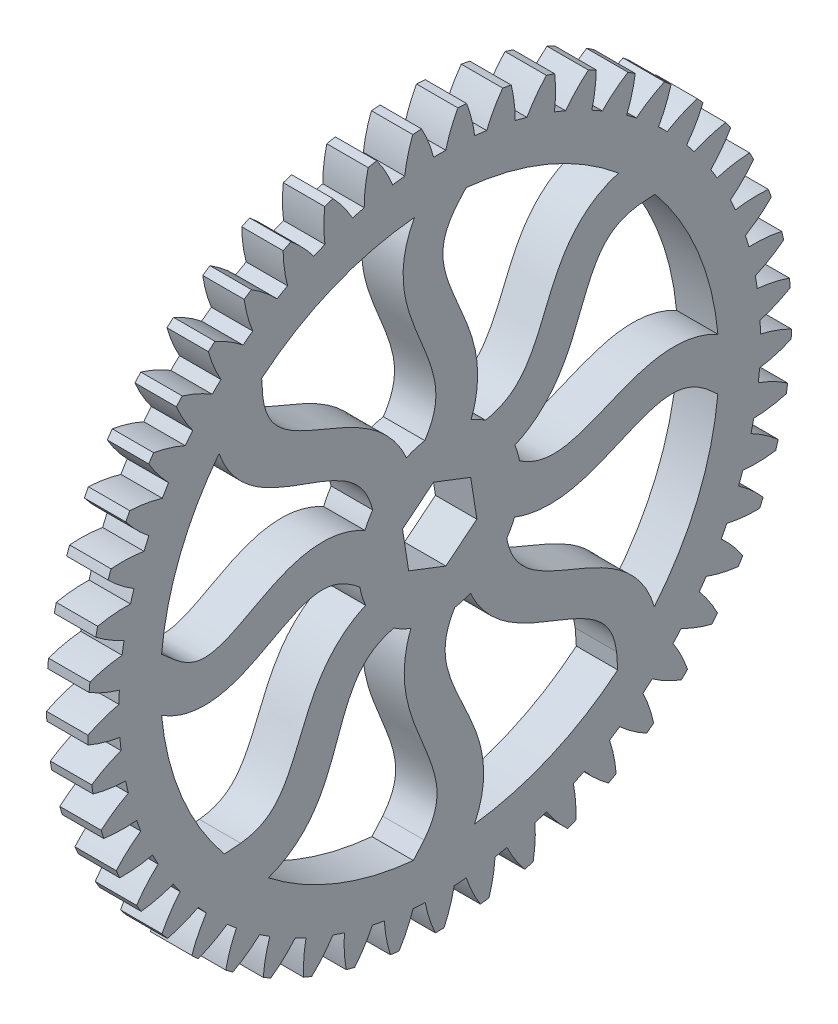
SolidWorks part; units mm, degrees
material "Plain Carbon Steel"
ref_plane "Plane1" through (0, 0, 0) normal (0, 0, 1) x (1, 0, 0)
ref_plane "Plane2" through (0, 0, 0) normal (0, 1, 0) x (1, 0, 0)
ref_plane "Plane3" through (0, 0, 0) normal (1, 0, 0) x (0, 0, -1)
sketch "HoldingSke" plane through (0, 0, 0) normal (0, 1, 0) x (1, 0, 0)
  line L0 (0, 0) -> (0.6561, -0.7547)
  line L1 (-15, 0) -> (100, 0) construction
  line L2 (0, 0) -> (-2.1039, 2.3779)
  line L3 (0, 0) -> (-11.863, 4.5341)
  line L4 (0, 0) -> (5.6657, 6.5177)
  line L5 (0, 0) -> (-46.8476, -17.4728)
  line L6 (0, 0) -> (-2.4869, -1.6779)
  line L7 (-2.1039, 2.3779) -> (8.6586, 51.2059)
  line L8 (-76.2, 54.61) -> (-75.7, 54.61)
  line L9 (-71.009, 38.7566) -> (-53.1078, 45.2721)
  line L10 (-76.2, 71.12) -> (104.1128, 71.12)
  line L11 (0, 0) -> (-3, 0)
  line L12 (-76.2, 101.6) -> (-76.162, 101.6)
  line L13 (24.9733, 27.94) -> (52.9518, 28.4284)
  line L14 (24.9733, 27.94) -> (24.9743, 27.94)
  line L15 (24.9733, 27.94) -> (100.4006, 29.5858)
  line L16 (-63.627, -1) -> (-12.827, -1)
  circle A0 centre (0, 0) radius 1.5
  circle A1 centre (0, 0) radius 23.249
  circle A2 centre (0, 0) radius 37.5
  circle A3 centre (0, 0) radius 1.5
  dimension "MHD" = 46.498
  dimension "Hub_dia" = 75
  dimension "Bore" = 3
  dimension "MBD" = 3
  dimension "Num_teeth" = 49
  dimension "Pitch_radius" = 180.3128
  dimension "Pitch" = 1
  dimension "Width" = 3
  dimension "Overall_len" = 50
  dimension "Show_teeth" = 49
  dimension "Thickness" = 3
  dimension "OAL" = 50.0001
  dimension "T_dim" = 0.5
  dimension "Ap" = 20
  dimension "H" = 19.05
  dimension "Backlash" = 0.038
  dimension "Addendum_fac" = 1
  dimension "Dedendum_fac" = 1.25
  dimension "Clearance_fac" = 0.25
  dimension "Dedendum_add" = 0.001
  dimension "Module" = 1
sketch "BasProSke" plane through (0, 0, 0) normal (0, 1, 0) x (1, 0, 0)
  line L0 (-10, 0) -> (60, 0) construction
  line L1 (0, 0) -> (0, 25.5)
  line L2 (0, 0) -> (3, 0)
  line L3 (3, 0) -> (3, 25.5)
  line L4 (3, 25.5) -> (0, 25.5)
  dimension "Diameter" = 51
  dimension "Thickness" = 3
revolve "Base-Revolve" add sketch "BasProSke" angle 360 about L0
sketch "TooCutSke" plane through (0, 0, 0) normal (1, 0, 0) x (0, 0, -1)
  line L1 (0, 0) -> (0, 107) construction
  line L2 (0, 0) -> (-0.8518, 24.4852) construction
  line L3 (0, 0) -> (-3.1381, 48.8783) construction
  line L4 (-0.8518, 24.4852) -> (-1.569, 24.4391) construction
  arc A0 (0.4386, 23.2449) -> (-0.4386, 23.2449) centre (0, 0) ccw
  arc A1 (1.3315, 25.4906) -> (-1.3315, 25.4906) centre (0, 0) ccw
  circle A2 centre (0, 0) radius 24.5 construction
  circle A3 centre (0, 0) radius 23.0225 construction
  arc A4 (-0.4386, 23.2449) -> (-1.3315, 25.4906) centre (-9.9221, 20.7746) ccw
  arc A5 (1.3315, 25.4906) -> (0.4386, 23.2449) centre (9.9221, 20.7746) ccw
  dimension "Root_dia" = 46.498
  dimension "Overcut_dia" = 51.0508
  dimension "Pitch_dia" = 49
  dimension "Base_dia" = 46.0449
  dimension "Flank_rad" = 9.8
  dimension "Half_ang" = 3.673
  dimension "Half_CT" = 0.7188
extrude "ToothCut" cut sketch "TooCutSke" along normal through all
fillet "Breaks" [suppressed] radius 0.02 tangent propagation no
fillet "RootFillets" [suppressed] radius 0.251
pattern_circular "TeethCuts" count 49 every 7.347 about axis through (-10, 0, 0) along (1, 0, 0) of "ToothCut", "RootFillets", "Breaks"
sketch "HubNeaOneSke" plane through (0, 0, 0) normal (-1, 0, 0) x (0, 0, 1)
  circle A0 centre (0, 0) radius 23.249
  dimension "Diameter" = 46.498
extrude "HubNearOne" [suppressed] add sketch "HubNeaOneSke" along normal blind 47.0001
sketch "HubNeaBotSke" plane through (0, 0, 0) normal (-1, 0, 0) x (0, 0, 1)
  circle A0 centre (0, 0) radius 23.249
  dimension "Diameter" = 46.498
extrude "HubNearBoth" [suppressed] add sketch "HubNeaBotSke" along normal blind 23.5
ref_plane "FarPln" through (3, 0, 0) normal (1, 0, 0) x (0, 0, -1)
sketch "HubFarSke" plane through (3, 0, 0) normal (1, 0, 0) x (0, 0, -1)
  circle A0 centre (0, 0) radius 23.249
  dimension "Diameter" = 46.498
extrude "HubFar" [suppressed] add sketch "HubFarSke" along normal blind 23.5
sketch "BorSke" plane through (0, 0, 0) normal (1, 0, 0) x (0, 0, -1)
  line L1 (-2.8868, 0) -> (-1.4434, -2.5) construction
  line L2 (-1.4434, -2.5) -> (1.4434, -2.5) construction
  line L3 (1.4434, -2.5) -> (2.8868, 0) construction
  line L4 (2.8868, 0) -> (1.4434, 2.5) construction
  line L5 (1.4434, 2.5) -> (-1.4434, 2.5) construction
  line L6 (-1.4434, 2.5) -> (-2.8868, 0) construction
  circle A0 centre (0, 0) radius 1.5
  circle A1 centre (0, 0) radius 2.5 construction
  dimension "D1" = 5
  dimension "Diameter" = 3
extrude "Bore" cut sketch "BorSke" along normal mid plane 100.0001
sketch "KeySke" plane through (0, 0, 0) normal (1, 0, 0) x (0, 0, -1)
  line L0 (-0.6, 0) -> (-0.6, 2)
  line L1 (-0.6, 2) -> (0.6, 2)
  line L2 (0.6, 2) -> (0.6, 0)
  line L3 (0, 0) -> (0, 34) construction
  line L4 (-0.6, 0) -> (0.6, 0)
  dimension "Offset" = 2
  dimension "Width" = 1.2
extrude "Keyway" [suppressed] cut sketch "KeySke" along normal mid plane 100.0001
pattern_circular "Keyway2" [suppressed] count 2 every 90 about axis through (-10, 0, 0) along (1, 0, 0)
sketch "Sketch1" plane through (0, 0, 0) normal (-1, 0, 0) x (0, 0, 1)
  line L0 (2.8868, 0) -> (5.8868, 0) construction
  line L1 (20.249, 0) -> (5.8868, 0) construction
  line L2 (20.249, 0) -> (23.249, 0) construction
  line L3 (19.2628, 1.1302) -> (20.1585, 1.9118)
  line L4 (5.7215, -1.1285) -> (4.8183, -3.3819)
  line L5 (14.42, -12.8217) -> (15.6061, -12.9024)
  line L6 (3.2477, -4.8436) -> (1.0157, -5.7985)
  line L7 (1.1302, -19.2628) -> (1.9118, -20.1585)
  line L8 (-1.1285, -5.7215) -> (-3.3819, -4.8183)
  line L9 (-12.8217, -14.42) -> (-12.9024, -15.6061)
  line L10 (-4.8436, -3.2477) -> (-5.7985, -1.0157)
  line L11 (-19.2628, -1.1302) -> (-20.1585, -1.9118)
  line L12 (-5.7215, 1.1285) -> (-4.8183, 3.3819)
  line L13 (-14.42, 12.8217) -> (-15.6061, 12.9024)
  line L14 (-3.2477, 4.8436) -> (-1.0157, 5.7985)
  line L15 (-1.1302, 19.2628) -> (-1.9118, 20.1585)
  line L16 (1.1285, 5.7215) -> (3.3819, 4.8183)
  line L17 (11.1265, 15.7649) -> (11.0739, 16.9526) [skipped]
  line L18 (4.4496, 3.7696) -> (5.6483, 1.6585) [skipped]
  line L19 (2.685, -5.1768) -> (0.3601, -5.8757) [skipped]
  line L20 (-5.3883, 18.5283) -> (-6.3496, 19.2277) [skipped]
  line L21 (12.8938, -14.3556) -> (14.0634, -14.5686) [skipped]
  line L22 (-2.3733, -5.3269) -> (-4.3693, -3.945) [skipped]
  line L23 (-5.6445, -1.4657) -> (-5.8085, 0.9564) [skipped]
  line L24 (-4.6652, 3.4992) -> (-2.8738, 5.1376) [skipped]
  line L25 (-0.173, 5.8291) -> (2.2249, 5.4501) [skipped]
  line L26 (-17.8456, 7.3395) -> (-18.9917, 7.024) [skipped]
  line L27 (-16.8648, -9.3761) -> (-17.3327, -10.469) [skipped]
  line L28 (-3.1845, -19.0313) -> (-2.6218, -20.0786) [skipped]
  line L29 (12.8217, 14.42) -> (12.9024, 15.6061)
  line L30 (4.8436, 3.2477) -> (5.7985, 1.0157)
  circle A0 centre (0, 0) radius 5.8868
  circle A1 centre (0, 0) radius 23.249 construction
  circle A2 centre (0, 0) radius 20.249
  spline S0 degree 3 poles (20.249, 0) (14.621, -4.9109) (10.9351, 5.4308) (4.7333, 0) knots 0 0 0 0 1 1 1 1 construction
  spline S1 degree 1 poles (19.2628, 1.1302) (3.7451, 1.1285) knots 0 0 1 1 construction
  spline S2 degree 3 poles (19.2628, 1.1302) (19.1293, 1.0138) (18.8376, 0.7808) (18.3339, 0.4567) (17.7715, 0.2166) (17.178, 0.1175) (16.3645, 0.1613) (15.163, 0.5668) (13.4561, 1.4991) (11.5183, 2.5306) (9.5885, 3.1305) (7.8275, 3.1388) (6.4544, 2.8313) (5.3119, 2.2876) (4.4177, 1.687) (3.9611, 1.3177) (3.7451, 1.1285) knots 0 0 0 0 0.03125 0.0625 0.125 0.1875 0.25 0.375 0.5 0.625 0.75 0.8125 0.875 0.9375 0.96875 1 1 1 1 only from (19.2628, 1.1302) to (5.4145, 2.3102)
  spline S3 degree 1 poles (21.2352, -1.1302) (5.7215, -1.1285) knots 0 0 1 1 construction
  spline S4 degree 3 poles (21.2352, -1.1302) (21.0332, -1.3065) (20.6054, -1.6485) (19.7572, -2.1994) (18.2169, -2.8765) (16.0114, -2.9359) (13.8328, -2.1307) (11.9654, -1.1014) (10.276, -0.2178) (9.0516, 0.1315) (8.1569, 0.1303) (7.4619, -0.0214) (6.7968, -0.3317) (6.2097, -0.7234) (5.8756, -0.9935) (5.7215, -1.1285) knots 0 0 0 0 0.03125 0.0625 0.125 0.25 0.375 0.5 0.625 0.75 0.8125 0.875 0.9375 0.96875 1 1 1 1 only from (20.1564, -1.9342) to (5.7215, -1.1285)
  spline S5 degree 3 poles (14.42, -12.8217) (14.2582, -12.8026) (13.9229, -12.7485) (13.3679, -12.6041) (12.7932, -12.3588) (12.2429, -11.9773) (11.6038, -11.331) (10.9146, -10.2125) (10.1792, -8.4567) (9.3709, -6.4927) (8.2199, -4.4964) (6.6749, -3.0349) (5.2192, -2.3229) (4.4625, -2.0781) (4.0808, -1.9789) (3.8352, -1.9214) (3.651, -1.8843) (3.5434, -1.8646) knots 0 0 0 0 0.03125 0.0625 0.125 0.1875 0.25 0.375 0.5 0.625 0.75 0.875 0.9375 0.96875 0.97755 0.98653 1 1 1 1
  spline S6 degree 3 poles (13.7854, -16.3368) (13.5386, -16.2959) (13.1873, -16.2223) (12.7413, -16.0987) (12.4785, -16.0136) (11.9085, -15.8059) (10.665, -15.1995) (9.1813, -13.763) (8.1187, -11.7584) (7.4026, -9.7726) (6.7462, -7.9552) (6.0949, -6.7348) (5.4563, -5.9802) (4.8946, -5.5111) (4.3092, -5.1875) (3.7476, -4.9747) (3.4115, -4.8817) (3.2477, -4.8436) knots 0 0 0 0 0.03125 0.044052 0.059677 0.06749 0.125 0.25 0.375 0.5 0.625 0.75 0.8125 0.875 0.9375 0.96875 1 1 1 1
  spline S7 degree 3 poles (1.1302, -19.2628) (1.0293, -19.1349) (0.8304, -18.8595) (0.5401, -18.365) (0.3072, -17.7851) (0.1878, -17.1263) (0.1929, -16.2173) (0.4965, -14.9391) (1.2179, -13.1776) (2.0352, -11.2173) (2.6329, -8.9918) (2.5738, -6.8659) (2.048, -5.3331) (1.686, -4.6249) (1.4863, -4.2849) (1.3532, -4.0706) (1.2492, -3.9141) (1.1871, -3.824) knots 0 0 0 0 0.03125 0.0625 0.125 0.1875 0.25 0.375 0.5 0.625 0.75 0.875 0.9375 0.96875 0.97755 0.98653 1 1 1 1
  spline S8 degree 3 poles (-1.8041, -21.2996) (-1.9497, -21.0961) (-2.1461, -20.7958) (-2.374, -20.3929) (-2.4997, -20.147) (-2.7559, -19.597) (-3.2064, -18.289) (-3.2397, -16.224) (-2.5736, -14.0552) (-1.6758, -12.1447) (-0.8549, -10.3954) (-0.4525, -9.0719) (-0.3705, -8.0869) (-0.4359, -7.3579) (-0.6211, -6.7152) (-0.8677, -6.1676) (-1.0396, -5.8641) (-1.1285, -5.7215) knots 0 0 0 0 0.03125 0.044052 0.059677 0.06749 0.125 0.25 0.375 0.5 0.625 0.75 0.8125 0.875 0.9375 0.96875 1 1 1 1
  spline S9 degree 3 poles (-12.8217, -14.42) (-12.8, -14.2585) (-12.7405, -13.9241) (-12.5872, -13.3716) (-12.3325, -12.8009) (-11.9422, -12.2568) (-11.2856, -11.6282) (-10.1561, -10.9572) (-8.3887, -10.2503) (-6.4119, -9.4739) (-4.3973, -8.3554) (-2.911, -6.8341) (-2.1755, -5.3901) (-1.9185, -4.6375) (-1.8132, -4.2575) (-1.7517, -4.0128) (-1.7116, -3.8293) (-1.6902, -3.722) knots 0 0 0 0 0.03125 0.0625 0.125 0.1875 0.25 0.375 0.5 0.625 0.75 0.875 0.9375 0.96875 0.97755 0.98653 1 1 1 1
  spline S10 degree 3 poles (-15.8291, -14.3136) (-15.7999, -14.0651) (-15.7429, -13.7108) (-15.6403, -13.2595) (-15.5677, -12.993) (-15.387, -12.4139) (-14.8397, -11.1432) (-13.4744, -9.5937) (-11.5219, -8.4381) (-9.572, -7.6296) (-7.7874, -6.8885) (-6.599, -6.1806) (-5.8752, -5.5073) (-5.433, -4.9241) (-5.1373, -4.3242) (-4.9511, -3.7532) (-4.8739, -3.4131) (-4.8436, -3.2477) knots 0 0 0 0 0.03125 0.044052 0.059677 0.06749 0.125 0.25 0.375 0.5 0.625 0.75 0.8125 0.875 0.9375 0.96875 1 1 1 1
  spline S11 degree 3 poles (-19.2628, -1.1302) (-19.1332, -1.0314) (-18.8548, -0.8369) (-18.3556, -0.5547) (-17.772, -0.3312) (-17.1113, -0.2225) (-16.2025, -0.2423) (-14.9294, -0.5664) (-13.1798, -1.3163) (-11.233, -2.1652) (-9.0175, -2.7988) (-6.8908, -2.7741) (-5.3497, -2.2731) (-4.6358, -1.9227) (-4.2926, -1.7284) (-4.0761, -1.5988) (-3.918, -1.4974) (-3.827, -1.4367) knots 0 0 0 0 0.03125 0.0625 0.125 0.1875 0.25 0.375 0.5 0.625 0.75 0.875 0.9375 0.96875 0.97755 0.98653 1 1 1 1
  spline S12 degree 3 poles (-21.3142, 1.0716) (-21.1177, 1.2266) (-20.8269, 1.4369) (-20.4352, 1.6835) (-20.1955, 1.8206) (-19.6582, 2.1023) (-18.3727, 2.6138) (-16.3116, 2.7441) (-14.1139, 2.1806) (-12.1634, 1.3735) (-10.3774, 0.6356) (-9.0365, 0.2959) (-8.0487, 0.2602) (-7.3236, 0.3598) (-6.6903, 0.575) (-6.1549, 0.847) (-5.8598, 1.033) (-5.7215, 1.1285) knots 0 0 0 0 0.03125 0.044052 0.059677 0.06749 0.125 0.25 0.375 0.5 0.625 0.75 0.8125 0.875 0.9375 0.96875 1 1 1 1
  spline S13 degree 3 poles (-14.42, 12.8217) (-14.2585, 12.8) (-13.9241, 12.7405) (-13.3716, 12.5872) (-12.8009, 12.3325) (-12.2568, 11.9422) (-11.6282, 11.2856) (-10.9572, 10.1561) (-10.2503, 8.3887) (-9.4739, 6.4119) (-8.3554, 4.3973) (-6.8341, 2.911) (-5.3901, 2.1755) (-4.6375, 1.9185) (-4.2575, 1.8132) (-4.0128, 1.7517) (-3.8293, 1.7116) (-3.722, 1.6902) knots 0 0 0 0 0.03125 0.0625 0.125 0.1875 0.25 0.375 0.5 0.625 0.75 0.875 0.9375 0.96875 0.97755 0.98653 1 1 1 1
  spline S14 degree 3 poles (-14.3136, 15.8291) (-14.0651, 15.7999) (-13.7108, 15.7429) (-13.2595, 15.6403) (-12.993, 15.5677) (-12.4139, 15.387) (-11.1432, 14.8397) (-9.5937, 13.4744) (-8.4381, 11.5219) (-7.6296, 9.572) (-6.8885, 7.7874) (-6.1806, 6.599) (-5.5073, 5.8752) (-4.9241, 5.433) (-4.3242, 5.1373) (-3.7532, 4.9511) (-3.4131, 4.8739) (-3.2477, 4.8436) knots 0 0 0 0 0.03125 0.044052 0.059677 0.06749 0.125 0.25 0.375 0.5 0.625 0.75 0.8125 0.875 0.9375 0.96875 1 1 1 1
  spline S15 degree 3 poles (-1.1302, 19.2628) (-1.0314, 19.1332) (-0.8369, 18.8548) (-0.5547, 18.3556) (-0.3312, 17.772) (-0.2225, 17.1113) (-0.2423, 16.2025) (-0.5664, 14.9294) (-1.3163, 13.1798) (-2.1652, 11.233) (-2.7988, 9.0175) (-2.7741, 6.8908) (-2.2731, 5.3497) (-1.9227, 4.6358) (-1.7284, 4.2926) (-1.5988, 4.0761) (-1.4974, 3.918) (-1.4367, 3.827) knots 0 0 0 0 0.03125 0.0625 0.125 0.1875 0.25 0.375 0.5 0.625 0.75 0.875 0.9375 0.96875 0.97755 0.98653 1 1 1 1
  spline S16 degree 3 poles (1.0716, 21.3142) (1.2266, 21.1177) (1.4369, 20.8269) (1.6835, 20.4352) (1.8206, 20.1955) (2.1023, 19.6582) (2.6138, 18.3727) (2.7441, 16.3116) (2.1806, 14.1139) (1.3735, 12.1634) (0.6356, 10.3774) (0.2959, 9.0365) (0.2602, 8.0487) (0.3598, 7.3236) (0.575, 6.6903) (0.847, 6.1549) (1.033, 5.8598) (1.1285, 5.7215) knots 0 0 0 0 0.03125 0.044052 0.059677 0.06749 0.125 0.25 0.375 0.5 0.625 0.75 0.8125 0.875 0.9375 0.96875 1 1 1 1
  spline S17 degree 3 poles (12.8217, 14.42) (12.8026, 14.2582) (12.7485, 13.9229) (12.6041, 13.3679) (12.3588, 12.7932) (11.9773, 12.2429) (11.331, 11.6038) (10.2125, 10.9146) (8.4567, 10.1792) (6.4927, 9.3709) (4.4964, 8.2199) (3.0349, 6.6749) (2.3229, 5.2192) (2.0781, 4.4625) (1.9789, 4.0808) (1.9214, 3.8352) (1.8843, 3.651) (1.8646, 3.5434) knots 0 0 0 0 0.03125 0.0625 0.125 0.1875 0.25 0.375 0.5 0.625 0.75 0.875 0.9375 0.96875 0.97755 0.98653 1 1 1 1
  spline S18 degree 3 poles (16.3368, 13.7854) (16.2959, 13.5386) (16.2223, 13.1873) (16.0987, 12.7413) (16.0136, 12.4785) (15.8059, 11.9085) (15.1995, 10.665) (13.763, 9.1813) (11.7584, 8.1187) (9.7726, 7.4026) (7.9552, 6.7462) (6.7348, 6.0949) (5.9802, 5.4563) (5.5111, 4.8946) (5.1875, 4.3092) (4.9747, 3.7476) (4.8817, 3.4115) (4.8436, 3.2477) knots 0 0 0 0 0.03125 0.044052 0.059677 0.06749 0.125 0.25 0.375 0.5 0.625 0.75 0.8125 0.875 0.9375 0.96875 1 1 1 1
  dimension "D1" = 3
  dimension "D2" = 3
  dimension "D3" = 1.5
  dimension "D4" = 1.5
  dimension "D5" = 7
  dimension "D6" = 8
extrude "Cut-Extrude1" cut sketch "Sketch1" against normal blind 10 contours A2 S18 L30 S2 L3 | S5 L5 A2 S4 L4 | S7 L7 A2 S6 L6 | S9 L9 A2 S8 L8 | S11 L11 A2 S10 L10 | S13 L13 A2 S12 L12 | S15 L15 A2 S14 L14 | S17 L29 A2 S16 L16 region at (0, 5.1984, 13.9187) region at (0, -5.8765, 13.2791) region at (0, 13.3918, 5.9464) region at (0, -13.7392, 5.0688) region at (0, 13.728, -5.3138) region at (0, -13.3742, -6.1373) region at (0, 5.9497, -13.4646) region at (0, -5.3139, -13.728)
sketch "Sketch2" plane through (0, 0, 0) normal (-1, 0, 0) x (0, 0, 1)
  line L1 (2.6928, 1.0402) -> (0.4456, 2.8522)
  line L2 (0.4456, 2.8522) -> (-2.2472, 1.812)
  line L3 (-2.2472, 1.812) -> (-2.6928, -1.0402)
  line L4 (-2.6928, -1.0402) -> (-0.4456, -2.8522)
  line L5 (-0.4456, -2.8522) -> (2.2472, -1.812)
  line L6 (2.2472, -1.812) -> (2.6928, 1.0402)
  circle A0 centre (0, 0) radius 2.5 construction
  dimension "D1" = 5
extrude "Cut-Extrude2" cut sketch "Sketch2" against normal blind 10
ref_plane "Plane4" through (1.5, 0, 0) normal (-1, 0, 0) x (0, 0, 1)
equation "' \"Module@HoldingSke\" = 6.35"
equation "' \"Num_teeth@HoldingSke\" = 12"
equation "' \"Ap@HoldingSke\" =  20"
equation "' \"Width@HoldingSke\" = 0.5 * 25.4"
equation "' \"Hub_dia@HoldingSke\"= 1 * 25.4"
equation "' \"Overall_len@HoldingSke\" = 1.0 * 25.4"
equation "' \"Bore@HoldingSke\" = 0.75 * 25.4"
equation "' \"T_dim@HoldingSke\" = 0.1 * 25.4"
equation "' \"Width@KeySke\" = 0.25 * 25.4"
equation "' \"Show_teeth@HoldingSke\" = 13"
equation "' \"Backlash@HoldingSke\" = 0.009 * 25.4"
equation "' \"Addendum_fac@HoldingSke\" = 1.0"
equation "' \"Dedendum_fac@HoldingSke\" = 1.25"
equation "' \"Dedendum_add@HoldingSke\" = 0.00005 * 25.4"
equation "' \"Clearance_fac@HoldingSke\" = 0.25"
equation "\"Pitch@HoldingSke\" = 1 / \"Module@HoldingSke\""
equation "\"Overcut_dia@TooCutSke\" = (\"Num_teeth@HoldingSke\" + 2 * \"Addendum_fac@HoldingSke\") / \"Pitch@HoldingSke\" + 0.002 * 25.4"
equation "\"Pitch_dia@TooCutSke\" = \"Num_teeth@HoldingSke\" / \"Pitch@HoldingSke\""
equation "\"Base_dia@TooCutSke\" = \"Num_teeth@HoldingSke\" / \"Pitch@HoldingSke\" * cos((\"Ap@HoldingSke\"  * 3.14159265 / 180))"
equation "\"Root_dia@TooCutSke\" = (\"Num_teeth@HoldingSke\" + 2) / \"Pitch@HoldingSke\" - 2 * (\"Addendum_fac@HoldingSke\" + \"Dedendum_fac@HoldingSke\") / \"Pitch@HoldingSke\" - \"Dedendum_add@HoldingSke\" * 2"
equation "\"Half_ang@TooCutSke\" = 180 / \"Num_teeth@HoldingSke\""
equation "\"Half_CT@TooCutSke\" = \"Num_teeth@HoldingSke\" / \"Pitch@HoldingSke\" * sin((3.14159265 / 2 / \"Num_teeth@HoldingSke\")) / 2 - 7 * \"Backlash@HoldingSke\" / 4"
equation "\"Flank_rad@TooCutSke\" = \"Num_teeth@HoldingSke\" / \"Pitch@HoldingSke\" / 5"
equation "\"Radius@RootFillets\" = \"Clearance_fac@HoldingSke\" / \"Pitch@HoldingSke\" + \"Dedendum_add@HoldingSke\""
equation "\"Break_rad@Breaks\" = 0.02 / \"Pitch@HoldingSke\""
equation "\"Thickness@HoldingSke\" = \"Width@HoldingSke\""
equation "\"OAL@HoldingSke\" = \"Thickness@HoldingSke\""
equation "\"MHD@HoldingSke\" = (\"Num_teeth@HoldingSke\" + 2) / \"Pitch@HoldingSke\" - 2 * (\"Addendum_fac@HoldingSke\" + \"Dedendum_fac@HoldingSke\")  / \"Pitch@HoldingSke\" - \"Dedendum_add@HoldingSke\" * 2"
equation "\"MBD@HoldingSke\" = (\"Num_teeth@HoldingSke\" + 2) / \"Pitch@HoldingSke\" - 2 * (\"Addendum_fac@HoldingSke\" + \"Dedendum_fac@HoldingSke\")  / \"Pitch@HoldingSke\" - \"Dedendum_add@HoldingSke\" * 2 - 0.002 * 25.4"
equation "\"MHD@HoldingSke\" = ((sgn( \"MHD@HoldingSke\" - \"Hub_dia@HoldingSke\" )-1)*( \"MHD@HoldingSke\" - \"Hub_dia@HoldingSke\" ))/-2+ \"Hub_dia@HoldingSke\""
equation "\"MBD@HoldingSke\" = ((sgn( \"MBD@HoldingSke\" - \"Bore@HoldingSke\" )-1)*( \"MBD@HoldingSke\" - \"Bore@HoldingSke\" ))/-2+ \"Bore@HoldingSke\""
equation "\"OAL@HoldingSke\" = ((sgn( \"OAL@HoldingSke\" - \"Overall_len@HoldingSke\" )+1)*( \"OAL@HoldingSke\" - \"Overall_len@HoldingSke\" ))/2 + \"Overall_len@HoldingSke\" + 0.000002 * 25.4"
equation "\"Num_teeth@TeethCuts\" = int( \"Show_teeth@HoldingSke\" ) + 1"
equation "\"Num_teeth@TeethCuts\" = ((sgn( \"Num_teeth@TeethCuts\" - \"Num_teeth@HoldingSke\" )-1)*( \"Num_teeth@TeethCuts\" - \"Num_teeth@HoldingSke\" ))/-2+ \"Num_teeth@HoldingSke\""
equation "\"Num_teeth@TeethCuts\" = ((sgn( \"Num_teeth@TeethCuts\" - 2.0)+1)*( \"Num_teeth@TeethCuts\" - 2.0))/2 +2.0"
equation "\"Angle@TeethCuts\" = 360.0 / \"Num_teeth@HoldingSke\""
equation "\"Diameter@BasProSke\" = (\"Num_teeth@HoldingSke\" + 2 * \"Addendum_fac@HoldingSke\") / \"Pitch@HoldingSke\""
equation "\"Thickness@BasProSke\"  = \"Thickness@HoldingSke\""
equation "' \"Fillet_rad@BasProSke\" =  \"Thickness@HoldingSke\" * 0.05"
equation "\"MHD@HoldingSke\" = ((sgn( \"MHD@HoldingSke\" - \"Root_dia@TooCutSke\" )-1)*( \"MHD@HoldingSke\" - \"Root_dia@TooCutSke\" ))/-2+ \"Root_dia@TooCutSke\""
equation "\"Diameter@HubNeaOneSke\" = \"MHD@HoldingSke\""
equation "\"Length@HubNearOne\" = \"OAL@HoldingSke\" - \"Thickness@BasProSke\""
equation "\"Diameter@HubNeaBotSke\" = \"MHD@HoldingSke\""
equation "\"Length@HubNearBoth\" = ( \"OAL@HoldingSke\" - \"Thickness@BasProSke\" ) / 2.0"
equation "\"Thickness@FarPln\" = \"Thickness@BasProSke\""
equation "\"Diameter@HubFarSke\" = \"MHD@HoldingSke\""
equation "\"Length@HubFar\" = ( \"OAL@HoldingSke\" - \"Thickness@BasProSke\" ) / 2.0"
equation "\"Diameter@BorSke\" = \"MBD@HoldingSke\""
equation "\"D1@Bore\" = \"OAL@HoldingSke\" * 2.0"
equation "\"D1@Keyway\" = \"OAL@HoldingSke\" * 2.0"
equation "\"Offset@KeySke\" = \"T_dim@HoldingSke\" + \"MBD@HoldingSke\" / 2.0"
